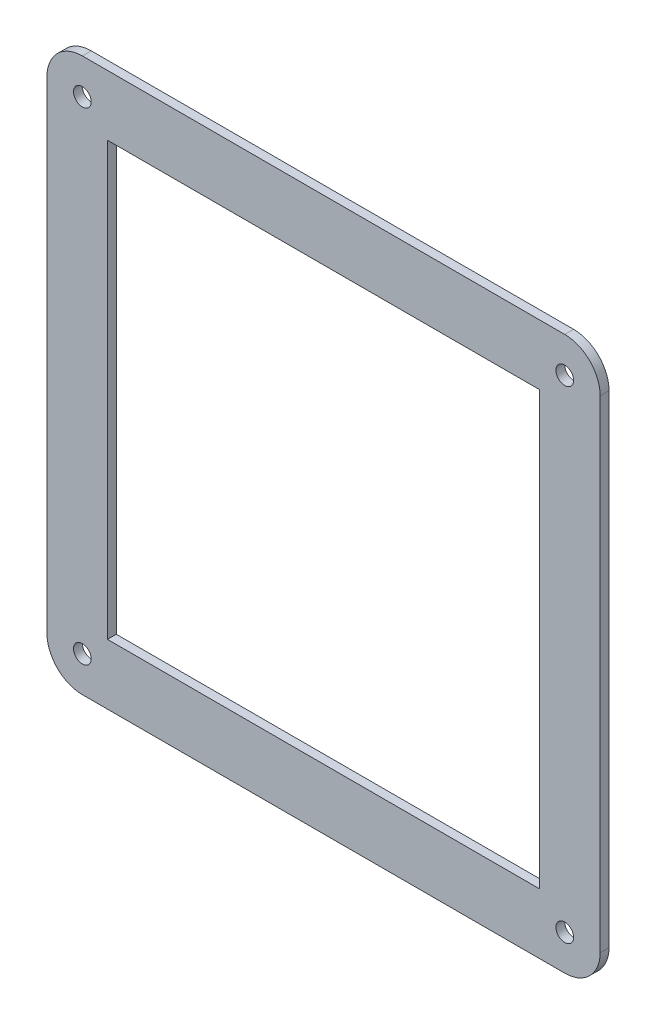
SolidWorks part; units mm, degrees
material "Plain Carbon Steel"
ref_plane "Front Plane" through (0, 0, 0) normal (0, 0, 1) x (1, 0, 0)
ref_plane "Top Plane" through (0, 0, 0) normal (0, 1, 0) x (1, 0, 0)
ref_plane "Right Plane" through (0, 0, 0) normal (1, 0, 0) x (0, 0, -1)
sketch "Sketch1" plane through (0, 0, 0) normal (0, 0, 1) x (1, 0, 0)
  line L0 (-97.6863, 97.6863) -> (97.6863, 97.6863)
  line L1 (-109, 125) -> (109, 125)
  line L2 (-125, 109) -> (-125, -109)
  line L3 (-109, -125) -> (109, -125)
  line L4 (125, 109) -> (125, -109)
  line L5 (-125, 125) -> (125, -125) construction
  line L6 (-125, -125) -> (125, 125) construction
  line L7 (97.6863, 97.6863) -> (97.6863, -97.6863)
  line L8 (97.6863, -97.6863) -> (-97.6863, -97.6863)
  line L9 (-97.6863, -97.6863) -> (-97.6863, 97.6863)
  arc A0 (-125, -109) -> (-109, -125) centre (-109, -109) ccw
  arc A1 (109, -125) -> (125, -109) centre (109, -109) ccw
  arc A2 (109, 125) -> (125, 109) centre (109, 109) cw
  arc A3 (-109, 125) -> (-125, 109) centre (-109, 109) ccw
  circle A4 centre (-109, 109) radius 16 construction
  circle A5 centre (-109, 109) radius 4
  circle A6 centre (109, 109) radius 4
  circle A7 centre (109, -109) radius 4
  circle A8 centre (-109, -109) radius 4
  point P0 (0, 0)
  point P19 (-97.6863, 97.6863)
  dimension "D3" = 16
  dimension "D4" = 8
  dimension "D5" = 8
  dimension "D6" = 8
  dimension "D7" = 8
  dimension "D1" = 250
  dimension "D2" = 250
extrude "Boss-Extrude1" add sketch "Sketch1" along normal blind 4
